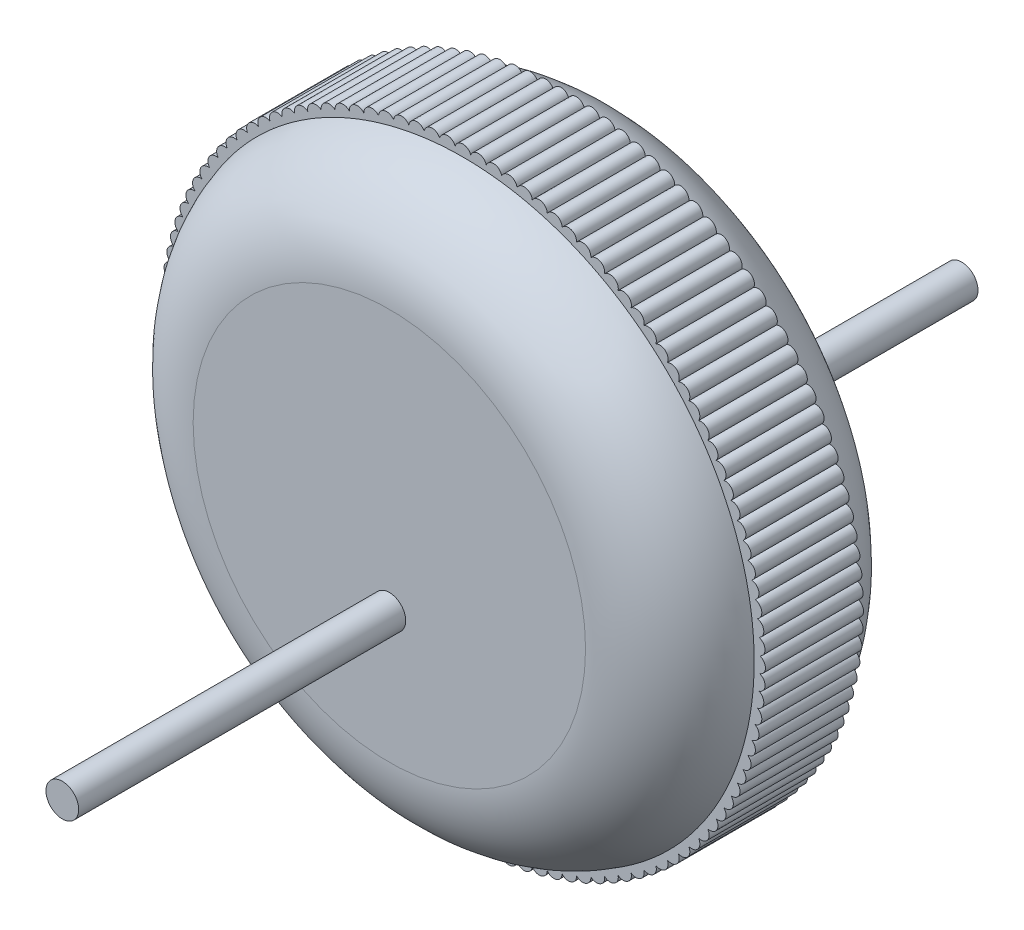
SolidWorks part; units mm, degrees
material "Silicon Rubber"
ref_plane "Front Plane" through (0, 0, 0) normal (0, 0, 1) x (1, 0, 0)
ref_plane "Top Plane" through (0, 0, 0) normal (0, 1, 0) x (1, 0, 0)
ref_plane "Right Plane" through (0, 0, 0) normal (1, 0, 0) x (0, 0, -1)
sketch "Sketch2" plane through (0, 0, 0) normal (0, 0, 1) x (1, 0, 0)
  circle A0 centre (0, 0) radius 9
  dimension "D1" = 18
extrude "Boss-Extrude1" add sketch "Sketch2" along normal mid plane 7.5
fillet "Fillet1" radius 3 2 edges at (9, 0, -3.75) (9, 0, 3.75)
sketch "Sketch3" plane through (0, 0, 0) normal (0, 0, 1) x (1, 0, 0)
  circle A0 centre (0, 9) radius 0.25
  circle A1 centre (0, 0) radius 9 construction
  dimension "D1" = 0.5
extrude "Boss-Extrude2" add sketch "Sketch3" along normal mid plane 3
pattern_circular "CirPattern1" count 120 over 360 about axis through (0, 0, 0.75) along (0, 0, -1) of "Boss-Extrude2"
sketch "Sketch4" plane through (0, 0, 3.75) normal (0, 0, 1) x (1, 0, 0)
  circle A0 centre (0, -2) radius 0.5
  point P2 (0, 0)
  dimension "D1" = 1
  dimension "D2" = 2
extrude "Boss-Extrude3" add sketch "Sketch4" along normal blind 10
sketch "Sketch5" plane through (0, 0, -3.75) normal (0, 0, -1) x (-1, 0, 0)
  circle A0 centre (0, -2) radius 0.5
  dimension "D1" = 1
  dimension "D2" = 2
extrude "Boss-Extrude4" add sketch "Sketch5" along normal blind 10
